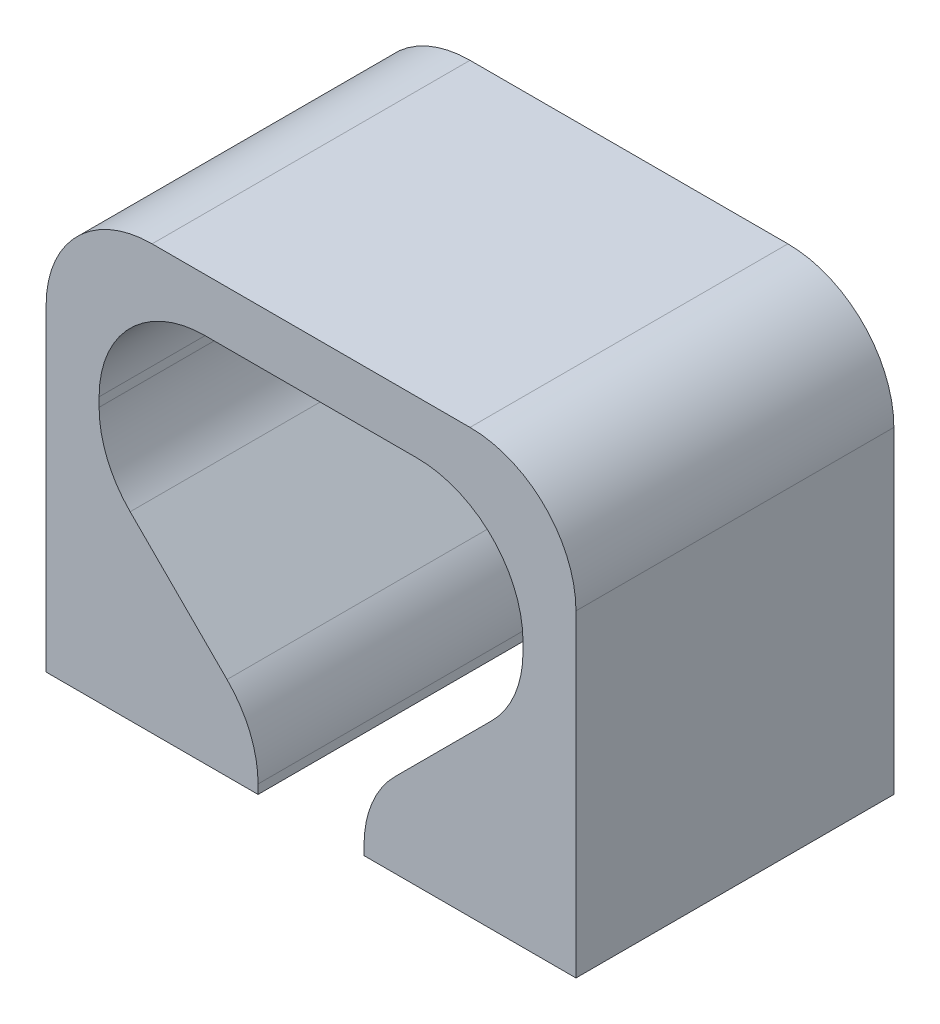
SolidWorks part; units mm, degrees
ref_plane "Front Plane" through (0, 0, 0) normal (0, 0, 1) x (1, 0, 0)
ref_plane "Top Plane" through (0, 0, 0) normal (0, 1, 0) x (1, 0, 0)
ref_plane "Right Plane" through (0, 0, 0) normal (1, 0, 0) x (0, 0, -1)
sketch "Sketch1" plane through (0, 0, 0) normal (0, 0, 1) x (1, 0, 0)
  line L0 (-12.5, 20) -> (12.5, 20)
  line L1 (12.5, 20) -> (12.5, 0)
  line L2 (12.5, 0) -> (2.5, 0)
  line L4 (10, 10) -> (10, 17.5)
  line L5 (10, 17.5) -> (-10, 17.5)
  line L6 (-10, 17.5) -> (-10, 10)
  line L8 (-2.5, 0) -> (-12.5, 0)
  line L9 (-12.5, 0) -> (-12.5, 20)
  line L10 (-2.5, 0) -> (2.5, 0) construction
  line L11 (-12.5, 10) -> (-10, 10) construction
  line L12 (10, 10) -> (-10, 10) construction
  line L13 (10, 10) -> (12.5, 10) construction
  line L14 (0, 20) -> (0, 17.5) construction
  line L15 (-10, 10) -> (-2.5, 2.5)
  line L16 (-2.5, 2.5) -> (-2.5, 0)
  line L17 (2.5, 0) -> (2.5, 2.5)
  line L18 (2.5, 2.5) -> (10, 10)
  line L19 (-2.5, 2.5) -> (2.5, 2.5) construction
  dimension "D1" = 2.5
  dimension "D2" = 25
  dimension "D3" = 20
  dimension "D4" = 5
  dimension "D5" = 10
  dimension "D6" = 2.5
extrude "Boss-Extrude1" add sketch "Sketch1" along normal blind 7.5 and the other way blind 7.5
fillet "Fillet1" radius 5 8 edges at (12.5, 20, 0) (-12.5, 20, 0) (10, 17.5, 0) (-10, 17.5, 0) (10, 10, 0) (2.5, 2.5, 0) (-2.5, 2.5, 0) (-10, 10, 0)
